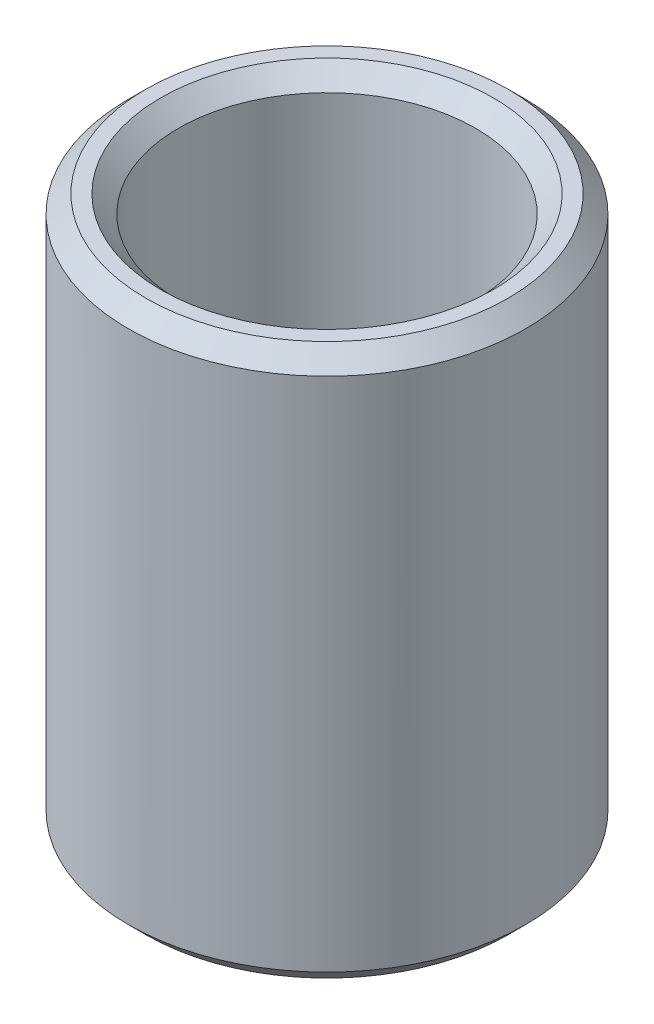
SolidWorks part; units mm, degrees
ref_plane "Front Plane" through (0, 0, 0) normal (0, 0, 1) x (1, 0, 0)
ref_plane "Top Plane" through (0, 0, 0) normal (0, 1, 0) x (1, 0, 0)
ref_plane "Right Plane" through (0, 0, 0) normal (1, 0, 0) x (0, 0, -1)
sketch "Sketch1" plane through (0, 0, 0) normal (0, 1, 0) x (1, 0, 0)
  circle A0 centre (0, 0) radius 42.5
  dimension "SLEEVE_OD" = 85
extrude "Boss-Extrude1" add sketch "Sketch1" along normal blind 117.9103
sketch "Sketch2" plane through (0, 0, 0) normal (0, 1, 0) x (1, 0, 0)
  circle A0 centre (0, 0) radius 31.795
  dimension "BORE_D" = 63.59
extrude "Cut-Extrude1" cut sketch "Sketch2" along normal through all
chamfer "Chamfer1" distance 3.7651 angle 45 4 edges at (0, 117.9103, 31.795) (0, 0, 31.795) (0, 0, 42.5) (0, 117.9103, 42.5)
